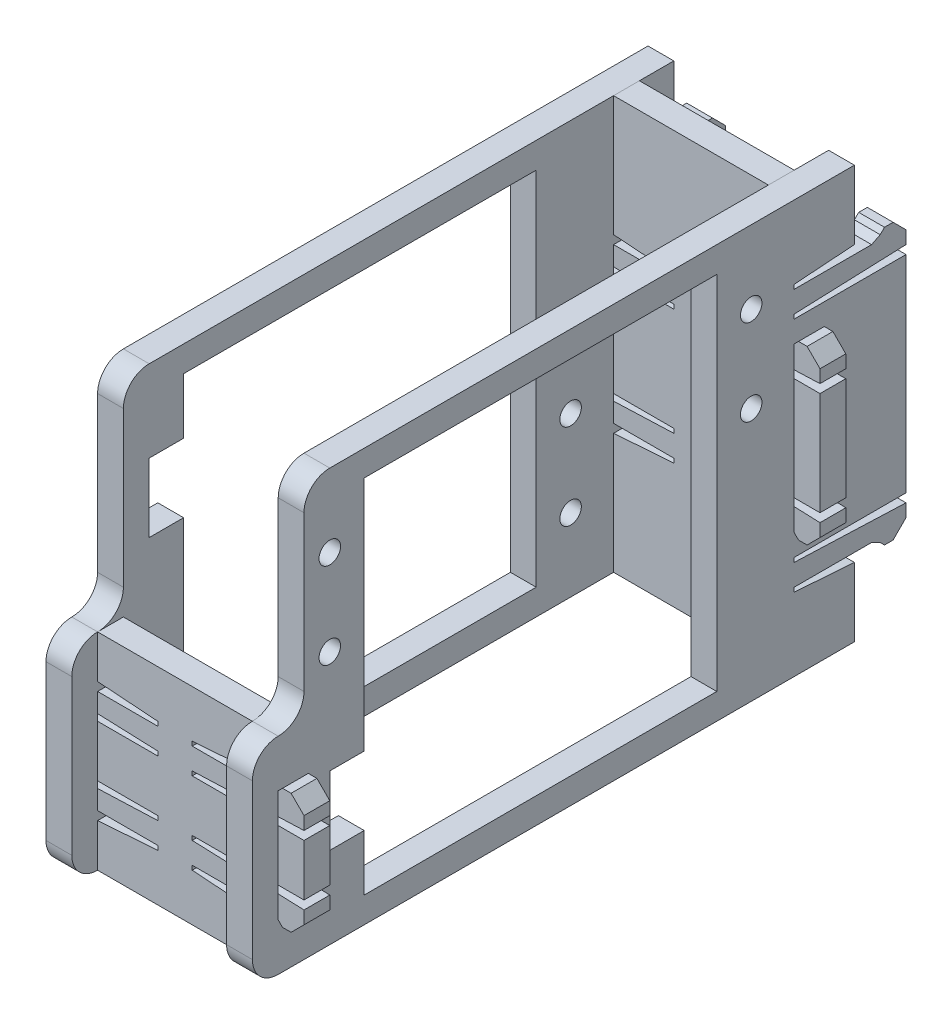
SolidWorks part; units mm, degrees
material "Lasercut ABS"
ref_plane "Front Plane" through (0, 0, 0) normal (0, 0, 1) x (1, 0, 0)
ref_plane "Top Plane" through (0, 0, 0) normal (0, 1, 0) x (1, 0, 0)
ref_plane "Right Plane" through (0, 0, 0) normal (1, 0, 0) x (0, 0, -1)
ref_plane "Plane1" through (9, 0, 0) normal (1, 0, 0) x (0, 0, -1)
ref_plane "Plane2" through (-9, 0, 0) normal (1, 0, 0) x (0, 0, -1)
sketch "Sketch1" plane through (9, 0, 0) normal (1, 0, 0) x (0, 0, -1)
  line L0 (-20.5, 0) -> (20.5, 0) construction
  line L1 (-20.5, -21) -> (20.5, -21)
  line L2 (-20.5, -21) -> (-20.5, -14.5)
  line L3 (-20.5, 21) -> (20.5, 21)
  line L4 (20.5, -21) -> (20.5, 21)
  line L5 (-20.5, -21) -> (20.5, 21) construction
  line L6 (-20.5, 21) -> (20.5, -21) construction
  line L7 (0, 0) -> (0, 21) construction
  line L8 (-24.5, 5.5) -> (-24.5, 15.5) construction
  line L9 (-24.5, 10.5) -> (24.5, 10.5) construction
  line L10 (24.5, 15.5) -> (24.5, 5.5) construction
  line L11 (-20.5, -6.5) -> (-20.5, 21)
  line L12 (-24.5, -6.5) -> (-20.5, -6.5)
  line L13 (-24.5, -6.5) -> (-24.5, -14.5)
  line L14 (-24.5, -14.5) -> (-20.5, -14.5)
  line L15 (0, 0) -> (0, -21) construction
  line L16 (-24.5, -10.5) -> (0, -10.5) construction
  line L17 (42.5, 12) -> (42.5, -12)
  line L18 (-27.5, 24) -> (36.5, 24)
  line L19 (-27.5, 24) -> (-27.5, -24)
  line L20 (-27.5, -24) -> (36.5, -24)
  line L21 (36.5, 24) -> (36.5, 16)
  line L22 (29.5, 9) -> (32.5, 9)
  line L23 (29.5, 9) -> (29.5, -9)
  line L24 (29.5, -9) -> (32.5, -9)
  line L25 (32.5, 9) -> (32.5, -9)
  line L26 (36.5, -16) -> (36.5, -24)
  circle A0 centre (-24.5, 15.5) radius 1.25
  circle A1 centre (-24.5, 5.5) radius 1.25
  circle A2 centre (24.5, 15.5) radius 1.25
  circle A3 centre (24.5, 5.5) radius 1.25
  point P0 (0, 0)
  point P18 (0, 10.5)
  line B0 (29.5, -15.5) -> (36.5, -16)
  line B1 (29.5, -15) -> (29.5, -15.5)
  line B2 (38.5, -15) -> (29.5, -15)
  line B3 (39.5, -15.5) -> (38.5, -15)
  line B4 (40, -16) -> (39.5, -15.5)
  line B5 (41, -16) -> (40, -16)
  line B6 (42.5, -14.5) -> (41, -16)
  line B7 (42.5, -13) -> (42.5, -14.5)
  line B8 (29.5, -12) -> (29.5, -12.5)
  line B9 (29.5, -12.5) -> (42.5, -13)
  line B10 (42.5, -12) -> (29.5, -12)
  line B11 (42.5, 12) -> (29.5, 12)
  line B12 (29.5, 12) -> (29.5, 12.5)
  line B13 (29.5, 12.5) -> (42.5, 13)
  line B14 (42.5, 13) -> (42.5, 14.5)
  line B15 (42.5, 14.5) -> (41, 16)
  line B16 (41, 16) -> (40, 16)
  line B17 (40, 16) -> (39.5, 15.5)
  line B18 (39.5, 15.5) -> (38.5, 15)
  line B19 (38.5, 15) -> (29.5, 15)
  line B20 (29.5, 15) -> (29.5, 15.5)
  line B21 (29.5, 15.5) -> (36.5, 16)
  dimension "D3" = 2.5
  dimension "D1" = 41
  dimension "D2" = 42
  dimension "D4" = 10
  dimension "D5" = 49
  dimension "D6" = 8
  dimension "D7" = 4
  dimension "D8" = 3
  dimension "D9" = 3
  dimension "D10" = 3
  dimension "D11" = 9
  dimension "D12" = 3
  dimension "D13" = 3
  dimension "D14" = 3
  dimension "D15" = 9
sketch_block_instance "Block-Snap-L-1"
sketch_block "Block-Snap-L" parameters "D1"=13, "D2"=0.5, "D3"=1, "D4"=1.5, "D5"=1.5, "D6"=0.5, "D7"=1, "D8"=7, "D9"=1, "D10"=0.5, "D11"=1, "D12"=1.5, "D13"=2.5
sketch_block_instance "Block-Snap-R-1"
sketch_block "Block-Snap-R" parameters "D1"=13, "D2"=0.5, "D3"=1, "D4"=0.5, "D5"=1, "D6"=2.5, "D7"=1.5, "D8"=1.5, "D9"=1.5, "D10"=1, "D11"=0.5, "D12"=1, "D13"=7
extrude "Boss-Extrude1" add sketch "Sketch1" along normal blind 3 contours B20 B21 L21 L18 L19 L20 L26 B0 B1 B2 B3 B4 B5 B6 B7 B9 B8 B10 L17 B11 B12 B13 B14 B15 B16 B17 B18 B19 L22 L25 L24 L23 L14 L13 L12 L11 L3 L4 L1 L2 A0 A1 A2 A3
sketch "Sketch2" plane through (-9, 0, 0) normal (1, 0, 0) x (0, 0, -1)
  line L0 (36.5, 24) -> (36.5, 16) construction
  line L1 (-27.5, 24) -> (36.5, 24) construction
  line L2 (-27.5, 24) -> (-27.5, -24) construction
  line L3 (-27.5, -24) -> (36.5, -24) construction
  line L4 (-20.5, -21) -> (20.5, -21) construction
  line L5 (20.5, -21) -> (20.5, 21) construction
  line L6 (-20.5, 21) -> (20.5, 21) construction
  line L7 (32.5, 9) -> (32.5, -9) construction
  line L8 (29.5, 9) -> (32.5, 9) construction
  line L9 (29.5, 9) -> (29.5, -9) construction
  line L10 (29.5, -9) -> (32.5, -9) construction
  line L11 (36.5, -16) -> (36.5, -24) construction
  line L12 (36.5, 24) -> (36.5, 16)
  line L13 (-27.5, 24) -> (36.5, 24)
  line L14 (-27.5, 24) -> (-27.5, -24)
  line L15 (-27.5, -24) -> (36.5, -24)
  line L16 (-20.5, -21) -> (20.5, -21)
  line L17 (20.5, -21) -> (20.5, 21)
  line L18 (-20.5, 21) -> (20.5, 21)
  line L19 (32.5, 9) -> (32.5, -9)
  line L20 (29.5, 9) -> (32.5, 9)
  line L21 (29.5, 9) -> (29.5, -9)
  line L22 (29.5, -9) -> (32.5, -9)
  line L23 (36.5, -16) -> (36.5, -24)
  line L24 (42.5, -12) -> (42.5, 12)
  line L25 (-20.5, 21) -> (-20.5, 14.5)
  line L26 (-20.5, 14.5) -> (-24.5, 14.5)
  line L27 (-24.5, 14.5) -> (-24.5, 6.5)
  line L28 (-24.5, 6.5) -> (-20.5, 6.5)
  line L29 (-20.5, 6.5) -> (-20.5, -21)
  line L30 (-24.5, -6.5) -> (-20.5, -6.5) construction
  line L31 (-24.5, -6.5) -> (-24.5, -14.5) construction
  line L32 (-20.5, -21) -> (-20.5, -14.5) construction
  line L33 (0, 0) -> (0, -21) construction
  line L34 (24.5, -5.5) -> (24.5, -15.5) construction
  line L35 (24.5, -10.5) -> (-24.5, -10.5) construction
  line L36 (-24.5, -5.5) -> (-24.5, -15.5) construction
  line L37 (24.5, 15.5) -> (24.5, 5.5) construction
  circle A0 centre (24.5, -5.5) radius 1.25
  circle A1 centre (24.5, -15.5) radius 1.25
  circle A2 centre (-24.5, -15.5) radius 1.25
  circle A3 centre (-24.5, -5.5) radius 1.25
  circle A5 centre (24.5, 5.5) radius 1.25 construction
  circle A6 centre (24.5, 15.5) radius 1.25 construction
  point P35 (-24.5, -10.5)
  point P46 (0, -10.5)
  line B0 (42.5, 12) -> (29.5, 12)
  line B1 (29.5, 12) -> (29.5, 12.5)
  line B2 (29.5, 12.5) -> (42.5, 13)
  line B3 (42.5, 13) -> (42.5, 14.5)
  line B4 (42.5, 14.5) -> (41, 16)
  line B5 (41, 16) -> (40, 16)
  line B6 (40, 16) -> (39.5, 15.5)
  line B7 (39.5, 15.5) -> (38.5, 15)
  line B8 (38.5, 15) -> (29.5, 15)
  line B9 (29.5, 15) -> (29.5, 15.5)
  line B10 (29.5, 15.5) -> (36.5, 16)
  line B11 (29.5, -15.5) -> (36.5, -16)
  line B12 (29.5, -15) -> (29.5, -15.5)
  line B13 (38.5, -15) -> (29.5, -15)
  line B14 (39.5, -15.5) -> (38.5, -15)
  line B15 (40, -16) -> (39.5, -15.5)
  line B16 (41, -16) -> (40, -16)
  line B17 (42.5, -14.5) -> (41, -16)
  line B18 (42.5, -13) -> (42.5, -14.5)
  line B19 (29.5, -12) -> (29.5, -12.5)
  line B20 (29.5, -12.5) -> (42.5, -13)
  line B21 (42.5, -12) -> (29.5, -12)
sketch_block_instance "Block-Snap-R-3"
sketch_block_instance "Block-Snap-L-5"
extrude "Boss-Extrude2" add sketch "Sketch2" against normal blind 3 separate body contours B21 L24 B0 B1 B2 B3 B4 B5 B6 B7 B8 B9 B10 L12 L13 L14 L15 L23 B11 B12 B13 B14 B15 B16 B17 B18 B20 B19 A3 A2 A1 A0 L29 L28 L27 L26 L25 L18 L17 L16 L22 L21 L20 L19
sketch "Sketch3" plane through (0, 0, -29.5) normal (0, 0, -1) x (-1, 0, 0)
  line L0 (12, -9) -> (9, -9) construction
  line L2 (12, 9) -> (9, 9) construction
  line L3 (9, -12) -> (9, 12) construction
  line L4 (9, -10) -> (9, -24)
  line L5 (9, 10) -> (9, 24)
  line L6 (15, 6) -> (15, -6)
  line L7 (0, 15) -> (0, -6.6823) construction
  line L8 (-15, 6) -> (-15, -6)
  line L9 (-9, 10) -> (-9, 24)
  line L10 (-9, -10) -> (-9, -24)
  line L11 (-9, 24) -> (9, 24)
  line L12 (-9, -24) -> (9, -24)
  point P15 (0, 0)
  line B0 (2, -9.5) -> (9, -10)
  line B1 (2, -9) -> (2, -9.5)
  line B2 (11, -9) -> (2, -9)
  line B3 (12, -9.5) -> (11, -9)
  line B4 (12.5, -10) -> (12, -9.5)
  line B5 (13.5, -10) -> (12.5, -10)
  line B6 (15, -8.5) -> (13.5, -10)
  line B7 (15, -7) -> (15, -8.5)
  line B8 (2, -6) -> (2, -6.5)
  line B9 (2, -6.5) -> (15, -7)
  line B10 (15, -6) -> (2, -6)
  line B11 (15, 6) -> (2, 6)
  line B12 (2, 6) -> (2, 6.5)
  line B13 (2, 6.5) -> (15, 7)
  line B14 (15, 7) -> (15, 8.5)
  line B15 (15, 8.5) -> (13.5, 10)
  line B16 (13.5, 10) -> (12.5, 10)
  line B17 (12.5, 10) -> (12, 9.5)
  line B18 (12, 9.5) -> (11, 9)
  line B19 (11, 9) -> (2, 9)
  line B20 (2, 9) -> (2, 9.5)
  line B21 (2, 9.5) -> (9, 10)
  line B22 (-2, -9.5) -> (-9, -10)
  line B23 (-2, -9) -> (-2, -9.5)
  line B24 (-11, -9) -> (-2, -9)
  line B25 (-12, -9.5) -> (-11, -9)
  line B26 (-12.5, -10) -> (-12, -9.5)
  line B27 (-13.5, -10) -> (-12.5, -10)
  line B28 (-15, -8.5) -> (-13.5, -10)
  line B29 (-15, -7) -> (-15, -8.5)
  line B30 (-2, -6) -> (-2, -6.5)
  line B31 (-2, -6.5) -> (-15, -7)
  line B32 (-15, -6) -> (-2, -6)
  line B33 (-15, 6) -> (-2, 6)
  line B34 (-2, 6) -> (-2, 6.5)
  line B35 (-2, 6.5) -> (-15, 7)
  line B36 (-15, 7) -> (-15, 8.5)
  line B37 (-15, 8.5) -> (-13.5, 10)
  line B38 (-13.5, 10) -> (-12.5, 10)
  line B39 (-12.5, 10) -> (-12, 9.5)
  line B40 (-12, 9.5) -> (-11, 9)
  line B41 (-11, 9) -> (-2, 9)
  line B42 (-2, 9) -> (-2, 9.5)
  line B43 (-2, 9.5) -> (-9, 10)
  line M1 (-9, -9) -> (-9, 9)
  line M2 (-9, 9) -> (-12, 9)
  line M3 (-12, 9) -> (-12, -9)
  line M4 (-12, -9) -> (-9, -9)
sketch_block_instance "Block-Snap-L-17"
sketch_block_instance "Block-Snap-R-10"
sketch_block_instance "Block-Snap-L-19"
sketch_block_instance "Block-Snap-R-12"
extrude "Boss-Extrude3" add sketch "Sketch3" along normal blind 3 separate body contours L7 L11 L9 B43 B42 B41 B35 B34 B33 B32 B30 B31 B24 B23 B22 L10 L12 M1 | L11 L7 L12 L4 B0 B1 B2 B3 B4 B5 B6 B7 B9 B8 B10 L6 B11 B12 B13 B14 B15 B16 B17 B18 B19 B20 B21 L5 | B35 M1 M2 M3 | B40 B39 B38 B37 B36 B35 M3 M2 | B33 B32 M3 M1 | B33 L8 B32 M3 | B31 M1 M3 M4 | B31 B29 B28 B27 B26 B25 M3 M4
sketch "Sketch4" plane through (12, 0, 0) normal (1, 0, 0) x (0, 0, -1)
  line L0 (-27.5, -6) -> (-27.5, 0)
  line L1 (-27.5, -24) -> (-33.5, -24)
  line L2 (-27.5, -24) -> (-27.5, -18)
  line L3 (-27.5, 0) -> (-33.5, 0)
  line L4 (-33.5, -24) -> (-33.5, 0)
  line L5 (-27.5, -18) -> (-30.5, -18)
  line L6 (-27.5, 24) -> (-27.5, -24) construction
  line L7 (-27.5, -6) -> (-30.5, -6)
  line L8 (-30.5, -18) -> (-30.5, -6)
  dimension "D1" = 3
  dimension "D2" = 6
  dimension "D3" = 6
extrude "Boss-Extrude4" add sketch "Sketch4" against normal up to surface (3 mm away) up to face at (9, 0, -31)
sketch "Sketch5" plane through (-12, 0, 0) normal (-1, 0, 0) x (0, 0, 1)
  line L0 (33.5, 0) -> (27.5, 0) construction
  line L1 (33.5, -24) -> (33.5, 0) construction
  line L2 (27.5, -6) -> (30.5, -6) construction
  line L3 (30.5, -6) -> (30.5, -18) construction
  line L4 (30.5, -18) -> (27.5, -18) construction
  line L5 (33.5, 0) -> (27.5, 0)
  line L6 (33.5, -24) -> (33.5, 0)
  line L7 (27.5, -6) -> (30.5, -6)
  line L8 (30.5, -6) -> (30.5, -18)
  line L9 (30.5, -18) -> (27.5, -18)
  line L10 (33.5, -24) -> (27.5, -24)
  line L11 (27.5, -24) -> (27.5, -18)
  line L12 (27.5, -6) -> (27.5, 0)
extrude "Boss-Extrude6" add sketch "Sketch5" against normal up to surface (3 mm away) up to face at (-9, 0, -32.1429)
sketch "Sketch6" plane through (0, 0, 27.5) normal (0, 0, 1) x (1, 0, 0)
  line L0 (9, -6) -> (12, -6) construction
  line L1 (9, -18) -> (12, -18) construction
  line L2 (9, -24) -> (9, 0) construction
  line L3 (15, -9) -> (15, -15)
  line L4 (9, -19) -> (9, -24)
  line L5 (9, -5) -> (9, 0)
  line L7 (0, 2.9298) -> (0, -11.621) construction
  line L8 (-9, -5) -> (-9, 0)
  line L9 (-9, -19) -> (-9, -24)
  line L10 (-15, -9) -> (-15, -15)
  line L11 (-9, 0) -> (9, 0)
  line L12 (9, -24) -> (-9, -24)
  point P18 (0, 0)
  line B0 (15, -9) -> (2, -9)
  line B1 (2, -9) -> (2, -8.5)
  line B2 (2, -8.5) -> (15, -8)
  line B3 (15, -8) -> (15, -6.5)
  line B4 (15, -6.5) -> (13.5, -5)
  line B5 (13.5, -5) -> (12.5, -5)
  line B6 (12.5, -5) -> (12, -5.5)
  line B7 (12, -5.5) -> (11, -6)
  line B8 (11, -6) -> (2, -6)
  line B9 (2, -6) -> (2, -5.5)
  line B10 (2, -5.5) -> (9, -5)
  line B11 (2, -18.5) -> (9, -19)
  line B12 (2, -18) -> (2, -18.5)
  line B13 (11, -18) -> (2, -18)
  line B14 (12, -18.5) -> (11, -18)
  line B15 (12.5, -19) -> (12, -18.5)
  line B16 (13.5, -19) -> (12.5, -19)
  line B17 (15, -17.5) -> (13.5, -19)
  line B18 (15, -16) -> (15, -17.5)
  line B19 (2, -15) -> (2, -15.5)
  line B20 (2, -15.5) -> (15, -16)
  line B21 (15, -15) -> (2, -15)
  line B22 (-15, -9) -> (-2, -9)
  line B23 (-2, -9) -> (-2, -8.5)
  line B24 (-2, -8.5) -> (-15, -8)
  line B25 (-15, -8) -> (-15, -6.5)
  line B26 (-15, -6.5) -> (-13.5, -5)
  line B27 (-13.5, -5) -> (-12.5, -5)
  line B28 (-12.5, -5) -> (-12, -5.5)
  line B29 (-12, -5.5) -> (-11, -6)
  line B30 (-11, -6) -> (-2, -6)
  line B31 (-2, -6) -> (-2, -5.5)
  line B32 (-2, -5.5) -> (-9, -5)
  line B33 (-2, -18.5) -> (-9, -19)
  line B34 (-2, -18) -> (-2, -18.5)
  line B35 (-11, -18) -> (-2, -18)
  line B36 (-12, -18.5) -> (-11, -18)
  line B37 (-12.5, -19) -> (-12, -18.5)
  line B38 (-13.5, -19) -> (-12.5, -19)
  line B39 (-15, -17.5) -> (-13.5, -19)
  line B40 (-15, -16) -> (-15, -17.5)
  line B41 (-2, -15) -> (-2, -15.5)
  line B42 (-2, -15.5) -> (-15, -16)
  line B43 (-15, -15) -> (-2, -15)
  line M1 (12, -18) -> (12, -6)
  line M2 (12, -6) -> (9, -6)
  line M3 (9, -6) -> (9, -18)
  line M4 (9, -18) -> (12, -18)
sketch_block_instance "Block-Snap-R-8"
sketch_block_instance "Block-Snap-L-14"
sketch_block_instance "Block-Snap-R-13"
sketch_block_instance "Block-Snap-L-20"
extrude "Boss-Extrude7" add sketch "Sketch6" along normal blind 3 separate body contours L7 L11 L8 B32 B31 B30 B29 B28 B27 B26 B25 B24 B23 B22 L10 B43 B41 B42 B40 B39 B38 B37 B36 B35 B34 B33 L9 L12 | L11 L7 L12 L4 B11 B12 B13 B20 B19 B21 B0 B1 B2 B8 B9 B10 L5 M3 | B2 M3 M1 M2 | B6 B7 B2 B3 B4 B5 M2 M1 | B21 L3 B0 M1 | B21 B0 M1 M3 | B20 M3 M4 M1 | B20 B14 B15 B16 B17 B18 M1 M4
fillet "Fillet1" radius 3 4 edges at (10.5, -24, 33.5) (10.5, 0, 33.5) (10.5, 0, 27.5) (10.5, 24, 27.5)
fillet "Fillet2" radius 3 4 edges at (-10.5, -24, 33.5) (-10.5, 0, 33.5) (-10.5, 0, 27.5) (-10.5, 24, 27.5)
other "Save Bodies1"
